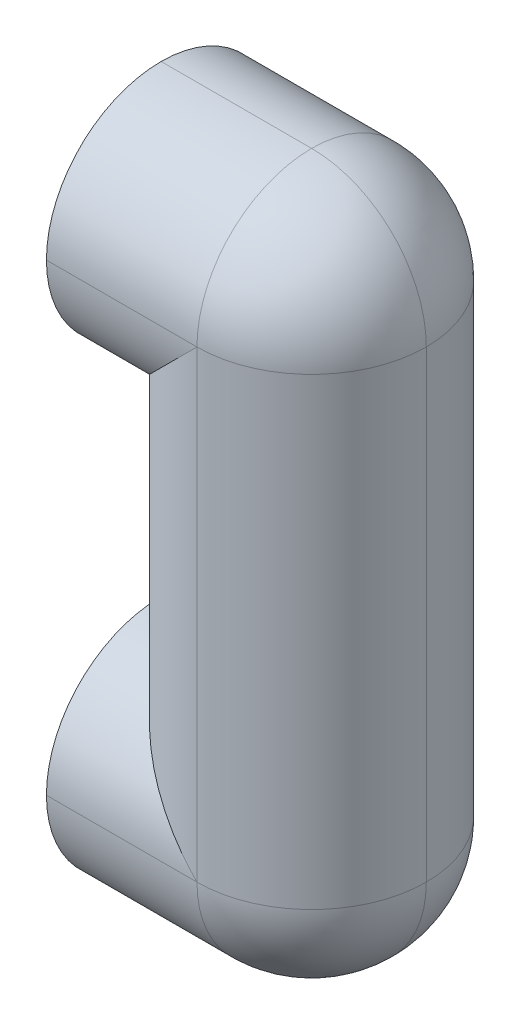
SolidWorks part; units mm, degrees
ref_plane "Front Plane" through (0, 0, 0) normal (0, 0, 1) x (1, 0, 0)
ref_plane "Top Plane" through (0, 0, 0) normal (0, 1, 0) x (1, 0, 0)
ref_plane "Right Plane" through (0, 0, 0) normal (1, 0, 0) x (0, 0, -1)
sketch "Sketch1" plane through (0, 0, 0) normal (0, 1, 0) x (1, 0, 0)
  line L1 (0, 0) -> (48, 0)
  line L2 (0, 0) -> (0, 48)
  line L3 (0, 48) -> (48, 48)
  line L4 (48, 0) -> (48, 48)
  dimension "D1" = 48
  dimension "D2" = 48
extrude "Boss-Extrude1" add sketch "Sketch1" along normal mid plane 145
sketch "Sketch2" plane through (0, 0, 0) normal (-1, 0, 0) x (0, 0, 1)
  line L0 (0, 72.5) -> (0, -72.5) construction
  line L1 (-48, 72.5) -> (0, 72.5)
  line L2 (-48, 72.5) -> (-48, 24.5)
  line L3 (-48, 24.5) -> (0, 24.5)
  line L4 (0, 72.5) -> (0, 24.5)
  line L6 (-48, -72.5) -> (0, -72.5)
  line L7 (-48, -72.5) -> (-48, -24.5)
  line L8 (-48, -24.5) -> (0, -24.5)
  line L9 (0, -72.5) -> (0, -24.5)
  dimension "D1" = 48
  dimension "D2" = 48
extrude "Boss-Extrude2" add sketch "Sketch2" along normal mid plane 15
fillet "Fillet1" radius 24 12 edges at (-3.75, -24.5, 0) (-3.75, -24.5, -48) (20.25, -72.5, -48) (20.25, -72.5, 0) (-3.75, 24.5, 0) (0, 0, 0) (0, 0, -48) (-3.75, 24.5, -48) (20.25, 72.5, -48) (20.25, 72.5, 0) (48, 0, -48) (48, 0, 0)
sketch "Sketch3" plane through (-7.5, 0, 0) normal (-1, 0, 0) x (0, 0, 1)
  circle A0 centre (-24, -48.5) radius 5
  dimension "D1" = 10
extrude "Cut-Extrude1" cut sketch "Sketch3" against normal blind 15
sketch "Sketch4" plane through (-7.5, 0, 0) normal (-1, 0, 0) x (0, 0, 1)
  circle A0 centre (-24, 48.5) radius 5
  dimension "D1" = 10
extrude "Boss-Extrude3" add sketch "Sketch4" along normal mid plane 15
